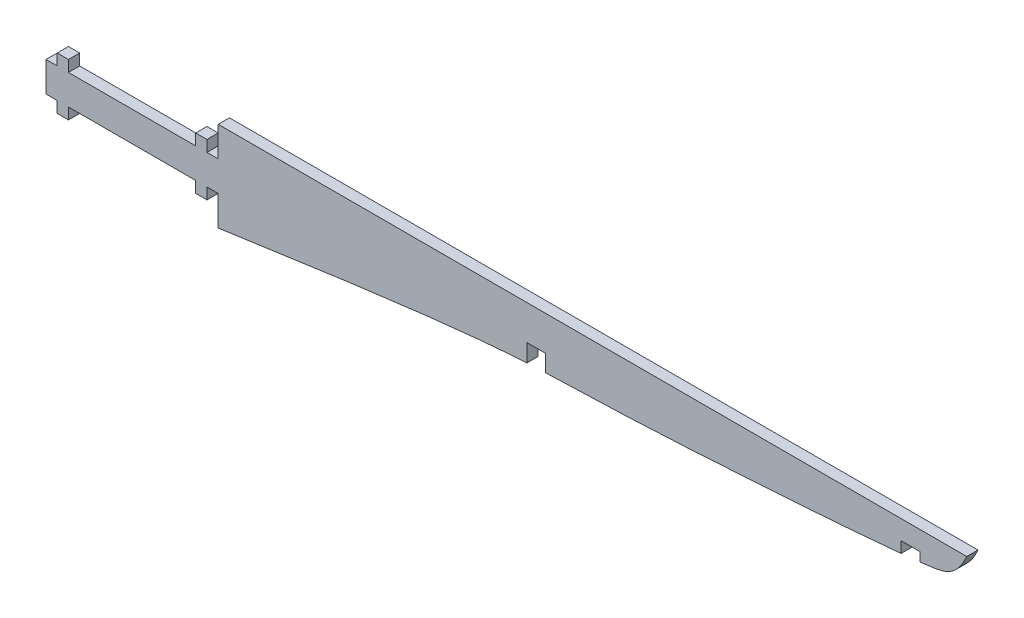
SolidWorks part; units mm, degrees
material "PC High Viscosity"
ref_plane "Front Plane" through (0, 0, 0) normal (0, 0, 1) x (1, 0, 0)
ref_plane "Top Plane" through (0, 0, 0) normal (0, 1, 0) x (1, 0, 0)
ref_plane "Right Plane" through (0, 0, 0) normal (1, 0, 0) x (0, 0, -1)
sketch "Sketch1" plane through (0, 0, 0) normal (0, 0, 1) x (1, 0, 0)
  line L0 (23, 0) -> (-23, 0) construction
  line L1 (-23, -4) -> (23, -4)
  line L2 (-23, -4) -> (-23, 4)
  line L3 (-23, 4) -> (23, 4)
  line L4 (23, -4) -> (23, 4)
  line L5 (-23, -4) -> (23, 4) construction
  line L6 (-23, 4) -> (23, -4) construction
  line L7 (17, 7) -> (20, 7)
  line L8 (17, 7) -> (17, -7)
  line L9 (17, -7) -> (20, -7)
  line L10 (20, 7) -> (20, -7)
  line L11 (0, 4) -> (0, -4) construction
  line L12 (-20, 7) -> (-20, -7)
  line L13 (-17, -7) -> (-20, -7)
  line L14 (-17, 7) -> (-17, -7)
  line L15 (-17, 7) -> (-20, 7)
  point P0 (0, 0)
  dimension "D1" = 8
  dimension "D2" = 46
  dimension "D3" = 3
  dimension "D4" = 3
  dimension "D5" = 3
extrude "Boss-Extrude1" add sketch "Sketch1" along normal blind 3 contours L14 L15 L12 L3 | L12 L3 L2 L1 | L14 L3 L12 L1 | L14 L1 L12 L13 | L3 L14 L1 L8 | L3 L10 L1 L4 | L10 L3 L8 L1 | L10 L7 L8 L3 | L10 L1 L8 L9 region at (-21.5, 0, 0) region at (-18.5, 0, 0) region at (-18.5, -5.5, 0) region at (0, 0, 0) region at (-18.5, 5.5, 0) region at (18.5, 0, 0) region at (18.5, -5.5, 0) region at (21.5, 0, 0) region at (18.5, 5.5, 0)
sketch "Sketch2" plane through (0, 0, 3) normal (0, 0, 1) x (1, 0, 0)
  line L0 (23, -12) -> (23, 12)
  line L1 (23, 12) -> (223, 12)
  line L2 (23, -4) -> (23, 4) construction
  line L3 (-23, 0) -> (23, 0) construction
  line L4 (-23, -4) -> (-23, 4) construction
  spline S0 degree 3 poles (223, 12) (221.1406, 7.8923) (218.7021, 6.1959) (212.7902, 3.9314) (103.0667, -3.7389) (102.0093, -0.4994) (23, -12) knots 0 0 0 0 0.169853 0.232552 0.58317 1 1 1 1
  dimension "D1" = 200
  dimension "D2" = 24
extrude "Boss-Extrude2" add sketch "Sketch2" against normal up to surface (3 mm away) up to face at (0, 0, 0)
sketch "Sketch4" plane through (0, 0, 3) normal (0, 0, 1) x (1, 0, 0)
  line L1 (105.4565, -8.7611) -> (110.4565, -8.7611)
  line L2 (105.4565, -8.7611) -> (105.4565, 2.7439)
  line L3 (105.4565, 2.7439) -> (110.4565, 2.7439)
  line L4 (110.4565, -8.7611) -> (110.4565, 2.7439)
  line L5 (205.4565, -8.7611) -> (210.4565, -8.7611)
  line L6 (205.4565, -8.7611) -> (205.4565, 6.8775)
  line L7 (205.4565, 6.8775) -> (210.4565, 6.8775)
  line L8 (210.4565, -8.7611) -> (210.4565, 6.8775)
  dimension "D1" = 5
  dimension "D2" = 100
extrude "Cut-Extrude1" cut sketch "Sketch4" against normal through all
equation "\"pulley_pitch_diam\"= 12.73mm"
equation "\"pulley_total_width\"= 16mm"
equation "\"pulley_total_diam\"= 16mm"
equation "\"belt_width\"= 6mm"
equation "\"material_thickness\"= 3mm"
equation "\"shaft_diam\"= 8mm"
equation "\"bearing_od\"= 22mm"
equation "\"bearing_thickness\"= 7mm"
equation "\"D1@Boss-Extrude1\"=\"material_thickness\""
equation "\"D5@Sketch1\"=\"material_thickness\""
